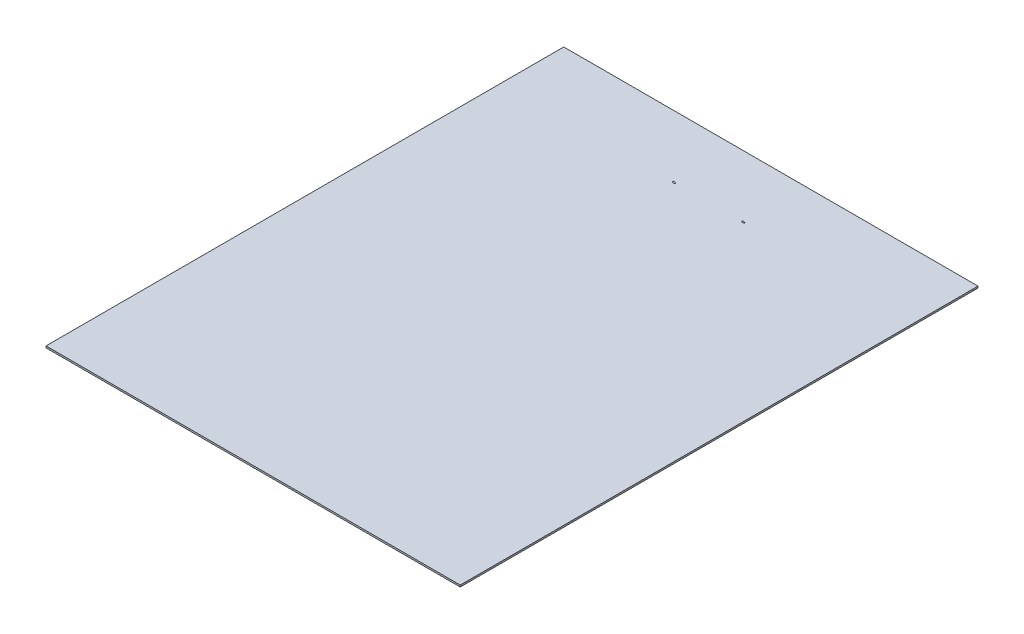
SolidWorks part; units mm, degrees
material "ABS"
ref_plane "Front Plane" through (0, 0, 0) normal (0, 0, 1) x (1, 0, 0)
ref_plane "Top Plane" through (0, 0, 0) normal (0, 1, 0) x (1, 0, 0)
ref_plane "Right Plane" through (0, 0, 0) normal (1, 0, 0) x (0, 0, -1)
sketch "Sketch1" plane through (0, 0, 0) normal (0, 1, 0) x (1, 0, 0)
  line L1 (-60, 75) -> (60, 75)
  line L2 (-60, 75) -> (-60, -75)
  line L3 (-60, -75) -> (60, -75)
  line L4 (60, 75) -> (60, -75)
  line L5 (-60, 75) -> (60, -75) construction
  line L6 (-60, -75) -> (60, 75) construction
  point P0 (0, 0)
  dimension "D1" = 120
  dimension "D2" = 150
extrude "Boss-Extrude1" add sketch "Sketch1" along normal blind 0.5
ref_plane "Plane1" through (10, 0, 0) normal (1, 0, 0) x (0, 0, -1)
sketch "Sketch3" plane through (10, 0, 0) normal (1, 0, 0) x (0, 0, -1)
  line L0 (75, 0.25) -> (57, 0.25) construction
  line L1 (75, 0.5) -> (75, 0) construction
  spline S0 degree 3 poles (57, 0.25) (39.2976, -24.7236) (0.2075, 4.9015) (-20.8796, -18.7699) knots 0 0 0 0 1 1 1 1
  point P7 (75, 0.25)
  dimension "D1" = 18
ref_plane "Plane2" through (-10, 0, 0) normal (1, 0, 0) x (0, 0, -1)
sketch "Sketch4" plane through (-10, 0, 0) normal (1, 0, 0) x (0, 0, -1)
  spline S0 degree 3 poles (-493.445, 1921.3285) (819.7385, -1972.9978) (-764.1762, 1958.0576) (475.0774, -1953.921) knots -2.119119 -2.119119 -2.119119 -2.119119 3.13711 3.13711 3.13711 3.13711 only from (57, 0.25) to (-20.8796, -18.7699) construction
  spline S1 degree 3 poles (57, 0.25) (39.2976, -24.7236) (0.2075, 4.9015) (-20.8796, -18.7699) knots 0 0 0 0 1 1 1 1
ref_point "Point1"
ref_point "Point2"
ref_plane "Plane4" through (0.0705, 0.3606, 20.5086) normal (0.0034, 0.0176, 0.9998) x (1, 0, -0.0034)
sketch "Sketch6" plane through (0.0705, 0.3606, 20.5086) normal (0.0034, 0.0176, 0.9998) x (1, 0, -0.0034)
  circle A0 centre (-10.0717, -19.1335) radius 0.525
  circle A1 centre (9.9282, -19.1347) radius 0.525
  dimension "D1" = 1.05
  dimension "D2" = 1.05
sweep "Sweep1" add profiles "Sketch6" path "Sketch4"
